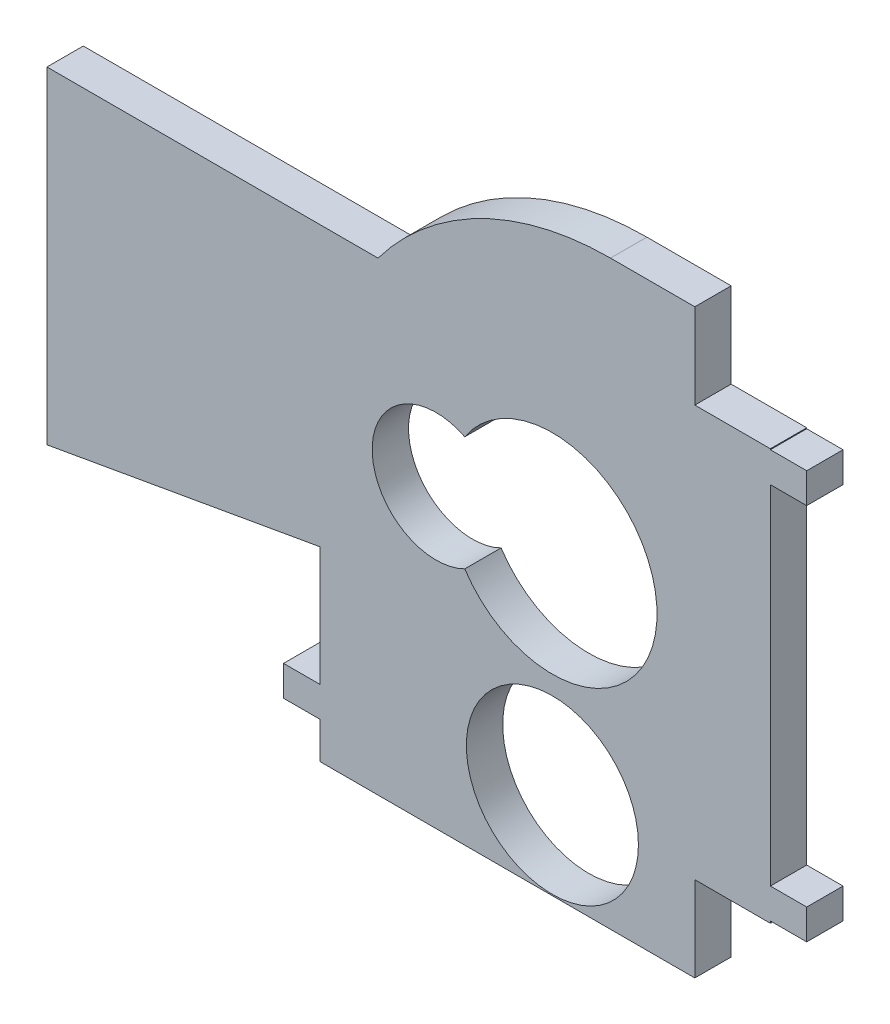
SolidWorks part; units mm, degrees
material "Balsa"
ref_plane "Front Plane" through (0, 0, 0) normal (0, 0, 1) x (1, 0, 0)
ref_plane "Top Plane" through (0, 0, 0) normal (0, 1, 0) x (1, 0, 0)
ref_plane "Right Plane" through (0, 0, 0) normal (1, 0, 0) x (0, 0, -1)
sketch "Sketch1" plane through (0, 0, 0) normal (0, 0, 1) x (1, 0, 0)
  line L0 (0, -1000.1535) -> (0, 48999.8465) construction
  line L1 (0, 9.144) -> (-5.08, 9.144) construction
  line L2 (-1000, 0) -> (49000, 0) construction
  line L3 (9.525, 16.51) -> (11.1125, 16.51)
  line L4 (2.54, 21.59) -> (9.525, 21.59)
  line L5 (-10.16, 8.89) -> (-10.16, -3.81)
  line L6 (-10.16, -3.81) -> (9.525, -3.81)
  line L7 (9.525, 21.59) -> (9.525, -3.81)
  line L8 (-11.7475, -2.2098) -> (-10.16, -2.2098)
  line L9 (-11.7475, -2.2098) -> (-11.7475, -0.889)
  line L10 (-11.7475, -0.889) -> (-10.16, -0.889)
  line L11 (-10.16, -2.2098) -> (-10.16, -0.889)
  line L12 (9.525, 0) -> (11.1125, 0)
  line L13 (9.525, 0) -> (9.525, 1.3208)
  line L14 (9.525, 1.3208) -> (11.1125, 1.3208)
  line L15 (11.1125, 0) -> (11.1125, 1.3208)
  line L16 (9.525, 16.51) -> (9.525, 17.8308)
  line L17 (9.525, 17.8308) -> (11.1125, 17.8308)
  line L18 (11.1125, 16.51) -> (11.1125, 17.8308)
  line L19 (-7.62, 16.51) -> (-22.0849, 16.51)
  line L21 (-22.0849, 2.212) -> (-10.16, 4.318)
  line L22 (9.525, 8.89) -> (-35.5862, 8.89) construction
  line L31 (-22.0849, 16.51) -> (-22.0849, 2.212)
  circle A0 centre (0, 0) radius 3.7592
  arc A1 (-3.829, 6.6457) -> (-3.829, 11.6423) centre (0, 9.144) ccw
  arc A2 (-3.829, 11.6423) -> (-3.829, 6.6457) centre (-5.08, 9.144) ccw
  arc A3 (2.54, 21.59) -> (-10.16, 8.89) centre (2.54, 8.89) ccw
  point P33 (9.525, 8.89)
  point P35 (-27.4189, 8.89)
  dimension "D1" = 7.5184
  dimension "D4" = 3.81
  dimension "D3" = 9.144
  dimension "D5" = 2.794
  dimension "D9" = 12.7
  dimension "D10" = 1.5875
  dimension "D2" = 25.4
  dimension "D6" = 9.525
  dimension "D7" = 5.08
  dimension "D8" = 19.685
  dimension "D11" = 9.144
  dimension "D12" = 1.3208
  dimension "D13" = 1.3208
  dimension "D14" = 1.5875
  dimension "D15" = 2
  dimension "D16" = 8.128
  dimension "D17" = 2.106
  dimension "D18" = 11.9249
  dimension "D19" = 5.08
  dimension "D20" = 5.207
extrude "Boss-Extrude1" add sketch "Sketch1" along normal blind 1.5875 contours L4 A3 L5 L6 L7 A0 A2 A1 | L10 L9 L8 L5 | L3 L18 L17 L7 | L12 L15 L14 L7 | A3 L19 L21 L5 | L21 region at (10.3187, 17.1704, 0) region at (9.2036, 8.9154, 0) region at (10.3187, 0.6604, 0) region at (-16.0223, 10.0529, 0) region at (-10.9538, -1.5494, 0)
sketch "Sketch2" plane through (0, 0, 1.5875) normal (0, 0, 1) x (1, 0, 0)
  line L0 (9.525, -0.9144) -> (9.525, -3.0226) construction
  line L1 (6.223, -3.8481) -> (9.525, -3.8481)
  line L2 (6.223, -3.8481) -> (6.223, -0.0889)
  line L3 (6.223, -0.0889) -> (9.525, -0.0889)
  line L4 (9.525, -3.8481) -> (9.525, -0.0889)
  line L5 (9.525, -0.9144) -> (9.525, -3.0226)
  line L6 (9.525, 20.8026) -> (9.525, 18.6944) construction
  line L7 (9.525, 20.8026) -> (9.525, 18.6944)
  line L9 (6.223, 17.8689) -> (9.525, 17.8689)
  line L10 (6.223, 17.8689) -> (6.223, 21.6281)
  line L11 (6.223, 21.6281) -> (9.525, 21.6281)
  line L12 (9.525, 17.8689) -> (9.525, 21.6281)
  point P8 (9.525, -1.9685)
  point P9 (9.525, -1.9685)
  point P10 (9.525, 19.7485)
  point P15 (9.525, 19.7485)
  line M4 (9.525, 21.59) -> (2.54, 21.59)
  line M11 (-10.16, -3.81) -> (9.525, -3.81)
  line M12 (9.525, -3.81) -> (9.525, 0)
  line M20 (9.525, 17.8308) -> (9.525, 21.59)
  dimension "D1" = 3.7592
  dimension "D2" = 3.302
  dimension "D3" = 3.7592
  dimension "D4" = 3.302
extrude "Cut-Extrude1" cut sketch "Sketch2" against normal up to next contours L3 L2 L4 M11 M12 | L10 L9 M20 M4 region at (7.874, -1.9495, 1.5875) region at (7.874, 19.7294, 1.5875)
move or copy body "Body-Move/Copy1" [suppressed]
